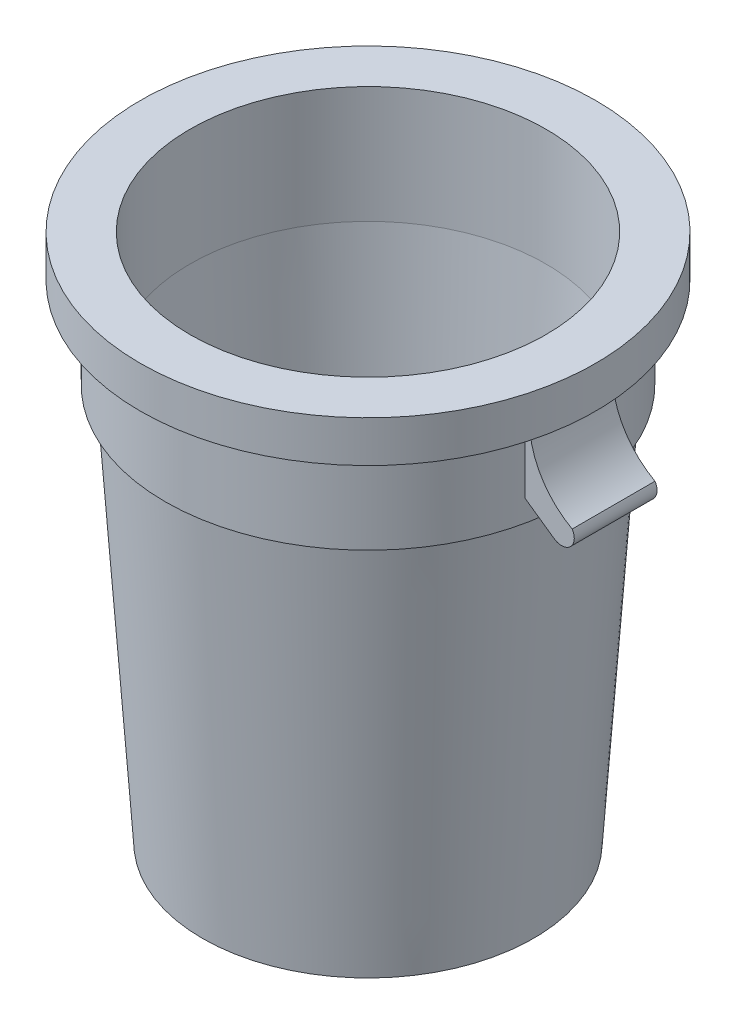
SolidWorks part; units mm, degrees
material "PE High Density"
ref_plane "Front Plane" through (0, 0, 0) normal (0, 0, 1) x (1, 0, 0)
ref_plane "Top Plane" through (0, 0, 0) normal (0, 1, 0) x (1, 0, 0)
ref_plane "Right Plane" through (0, 0, 0) normal (1, 0, 0) x (0, 0, -1)
sketch "Sketch1" plane through (0, 0, 0) normal (0, 0, 1) x (1, 0, 0)
  line L0 (0, 0) -> (203.2, 0)
  line L1 (203.2, 0) -> (236.22, 486.918)
  line L2 (236.22, 486.918) -> (248.92, 486.918)
  line L3 (248.92, 486.918) -> (248.92, 598.424)
  line L4 (248.92, 598.424) -> (254, 598.424)
  line L5 (279.4, 598.424) -> (279.4, 649.224)
  line L6 (279.4, 649.224) -> (218.4181, 649.224)
  line L7 (266.7, 598.424) -> (279.4, 598.424)
  line L9 (254, 598.424) -> (254, 617.474)
  line L10 (254, 617.474) -> (266.7, 617.474)
  line L11 (266.7, 598.424) -> (266.7, 617.474)
  line L12 (0, 19.05) -> (185.3981, 19.05)
  line L13 (185.3981, 19.05) -> (218.4181, 505.968)
  line L14 (0, 19.05) -> (0, 0)
  line L18 (234.95, 630.174) -> (234.95, 630.174)
  line L19 (234.95, 630.174) -> (234.95, 630.174)
  line L20 (234.95, 630.174) -> (234.95, 630.174)
  line L21 (234.95, 630.174) -> (234.95, 630.174)
  line L23 (218.4181, 505.968) -> (218.4181, 649.224)
  line L24 (234.95, 630.174) -> (0, 630.174) construction
  line L25 (279.4, 649.224) -> (0, 649.224) construction
  line L26 (229.87, 505.968) -> (229.87, 617.474) construction
  line L27 (234.95, 617.474) -> (234.95, 630.174) construction
  line L28 (229.87, 617.474) -> (234.95, 617.474) construction
  line L29 (218.4181, 505.968) -> (229.87, 505.968) construction
  dimension "D1" = 203.2
  dimension "D2" = 236.22
  dimension "D3" = 486.918
  dimension "D4" = 12.7
  dimension "D5" = 111.506
  dimension "D6" = 50.8
  dimension "D8" = 19.05
  dimension "D9" = 12.7
  dimension "D10" = 12.7
  dimension "D11" = 19.05
revolve "Revolve1" add sketch "Sketch1" angle 360 about L14 region at (7.0679, 9.525, 0)
sketch "Sketch2" plane through (0, 0, 0) normal (0, 0, 1) x (1, 0, 0)
  line L0 (248.92, 509.524) -> (279.4, 488.1817)
  line L1 (248.92, 486.918) -> (248.92, 598.424) construction
  line L3 (-279.4, 598.424) -> (279.4, 598.424) construction
  line L4 (-248.92, 598.424) -> (248.92, 598.424) construction
  line L8 (248.92, 509.524) -> (236.22, 518.4166)
  line L9 (236.22, 518.4166) -> (236.22, 598.424)
  line L10 (236.22, 598.424) -> (248.92, 598.424)
  arc A0 (248.92, 598.424) -> (301.3331, 509.524) centre (350.52, 598.424) ccw
  arc A1 (279.4, 488.1817) -> (301.3331, 509.524) centre (288.3344, 500.9413) ccw
  dimension "D1" = 101.6
  dimension "D2" = 88.9
extrude "Boss-Extrude1" add sketch "Sketch2" along normal blind 50.8 and the other way blind 50.8
